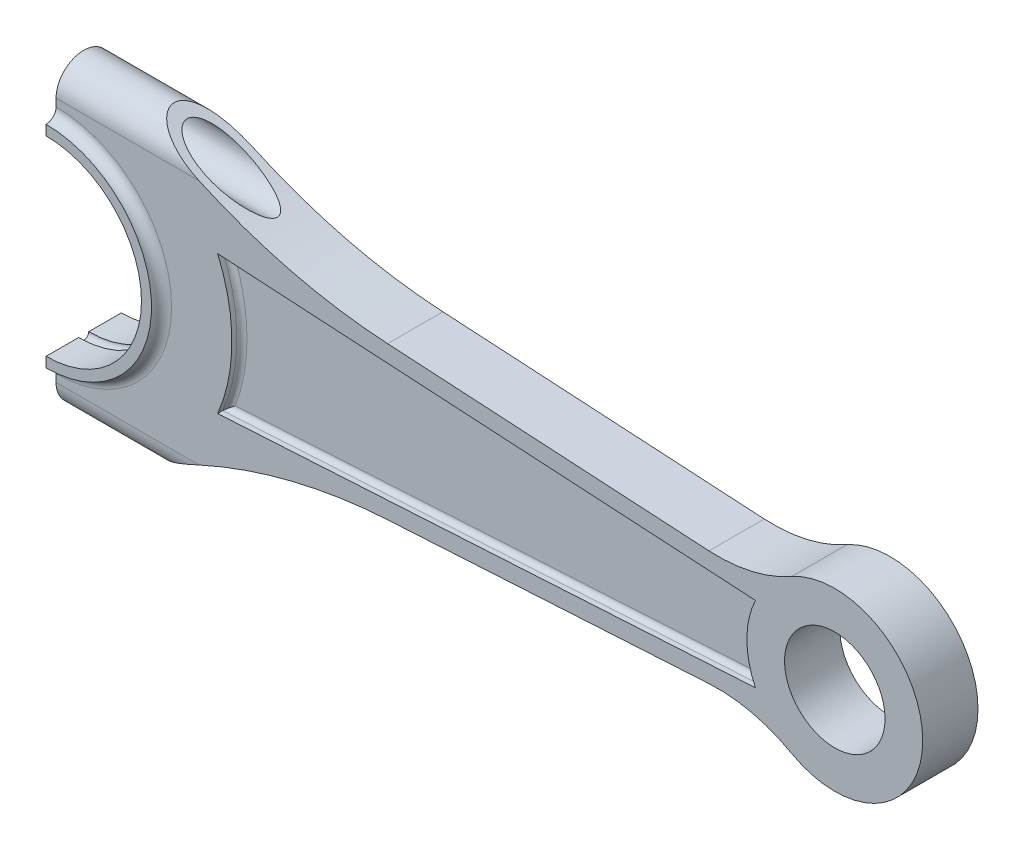
SolidWorks part; units mm, degrees
ref_plane "Front Plane" through (0, 0, 0) normal (0, 0, 1) x (1, 0, 0)
ref_plane "Top Plane" through (0, 0, 0) normal (0, 1, 0) x (1, 0, 0)
ref_plane "Right Plane" through (0, 0, 0) normal (1, 0, 0) x (0, 0, -1)
sketch "Sketch1" plane through (0, 0, 0) normal (0, 0, 1) x (1, 0, 0)
  line L0 (3937, 0) -> (0, 0) construction
  line L1 (-0.057, 762) -> (457.905, 762)
  line L2 (757.2512, 439.1989) -> (773.4704, 438.2517)
  line L3 (1676.1325, 385.5364) -> (3300.7334, 290.6599)
  line L4 (1676.1325, -385.5364) -> (3300.7334, -290.6599)
  line L5 (-0.057, -762) -> (457.905, -762)
  line L6 (-0.057, 762) -> (0, 482.6)
  line L7 (-0.057, -762) -> (0, -482.6)
  arc A0 (0, -482.6) -> (0, 482.6) centre (0, 0) ccw
  circle A1 centre (3937, 0) radius 254
  arc A2 (3718.9531, -387.3446) -> (3718.9531, 387.3446) centre (3937, 0) ccw
  arc A3 (457.905, 762) -> (457.905, -762) centre (0, 0) ccw construction
  arc A4 (3300.7334, 290.6599) -> (3718.9531, 387.3446) centre (3345.1584, 1051.3638) ccw
  arc A5 (457.905, 762) -> (1676.1325, 385.5364) centre (1831.62, 3048) ccw
  arc A6 (3300.7334, -290.6599) -> (3718.9531, -387.3446) centre (3345.1584, -1051.3638) cw
  arc A7 (457.905, -762) -> (1676.1325, -385.5364) centre (1831.62, -3048) cw
  dimension "D1" = 965.2
  dimension "D2" = 508
  dimension "D3" = 889
  dimension "D6" = 1778
  dimension "D9" = 762
  dimension "D10" = 2667
  dimension "D4" = 762
  dimension "D5" = 457.962
  dimension "D7" = 0
  dimension "D8" = 3937
extrude "Boss-Extrude1" add sketch "Sketch1" along normal mid plane 279.4 contours L5 A7 L4 A6 A2 A4 L3 A5 L1 L6 A0 L7 A1 region at (1893.6436, 0, 0)
sketch "Sketch3" plane through (0, 0, 139.7) normal (0, 0, 1) x (1, 0, 0)
  line L0 (3535.7201, -191.1929) -> (817.2234, -349.9527)
  line L1 (1676.1325, -385.5364) -> (3300.7334, -290.6599) construction
  line L2 (3937, 0) -> (0, 0) construction
  line L3 (3535.7201, 191.1929) -> (817.2234, 349.9527)
  arc A1 (3535.7201, 191.1929) -> (3535.7201, -191.1929) centre (3937, 0) ccw
  arc A2 (817.2234, -349.9527) -> (817.2234, 349.9527) centre (0, 0) ccw
  dimension "D1" = 1778
  dimension "D2" = 889
  dimension "D3" = 85.598
extrude "Cut-Extrude1" cut sketch "Sketch3" against normal blind 50.8 and the other way through all
sketch "Sketch4" plane through (0.0984, 0, 0) normal (-1, 0.0002, 0) x (0, 0, 1)
  line L0 (-139.7, 482.6) -> (139.7, 762) construction
  line L1 (-139.7, 762) -> (139.7, 482.6) construction
  line L2 (0, 0) -> (-973.0459, 0) construction
  circle A0 centre (0, 622.3) radius 63.5
  circle A1 centre (0, -622.3) radius 63.5
  dimension "D1" = 127
extrude "Cut-Extrude2" cut sketch "Sketch4" against normal through all both and the other way through all
sketch "Sketch5" plane through (0.0984, 0, 0) normal (-1, -0.0002, 0) x (0, 0, 1)
  circle A0 centre (0, 622.3) radius 101.6
  circle A1 centre (0, -622.3) radius 101.6
  dimension "D1" = 203.2
  dimension "D2" = 203.2
extrude "Cut-Extrude3" cut sketch "Sketch5" against normal through all from offset 508
sketch "Sketch6" plane through (0, 0, 139.7) normal (0, 0, 1) x (1, 0, 0)
  line L0 (-0.057, 762) -> (0, 482.6) construction
  line L1 (-0.057, -762) -> (0, -482.6) construction
  line L2 (-0.0104, 533.4) -> (0, 482.6)
  line L3 (0, -482.6) -> (-0.0104, -533.4)
  arc A0 (0, -482.6) -> (0, 482.6) centre (0, 0) ccw construction
  arc A1 (0, -482.6) -> (0, 482.6) centre (0, 0) ccw
  arc A2 (-0.0104, 533.4) -> (-0.0104, -533.4) centre (0, 0) cw
  dimension "D1" = 533.4
extrude "Boss-Extrude2" add sketch "Sketch6" along normal blind 50.8
mirror "Mirror1" about plane through (0, 0, 0) normal (0, 0, 1) of "Cut-Extrude1", "Boss-Extrude2"
fillet "Fillet1" radius 50.8 2 edges at (533.4, 0, -139.7) (533.4, 0, 139.7)
sketch "Sketch8" plane through (0.0984, 0, 0) normal (-1, -0.0002, 0) x (0, 0, 1)
  line L0 (190.5, 482.6) -> (-190.5, 482.6) construction
  line L1 (0, 0) -> (764.7578, 0) construction
  circle A0 centre (0, 482.6) radius 25.4
  dimension "D1" = 50.8
revolve "Cut-Revolve1" cut sketch "Sketch8" angle 360 about L1
fillet "Fillet3" radius 25.4 8 edges at (3492.5, 0, 88.9) (2176.4718, 270.5728, 88.9) (2176.4718, -270.5728, 88.9) (889, 0, 88.9) (2176.4718, -270.5728, -88.9) (889, 0, -88.9) (3492.5, 0, -88.9) (2176.4718, 270.5728, -88.9)
fillet "Fillet4" 2 edges at (228.924, 762, 139.7) (228.924, 762, -139.7) type full round first side face at (1626.8583, 0, 139.7) second side face at (2176.4718, 0, -139.7) middle face at (228.924, 762, 0)
fillet "Fillet5" 2 edges at (228.924, -762, 139.7) (228.924, -762, -139.7) type full round first side face at (1649.9448, -20.8142, 139.7) second side face at (2176.4718, 0, -139.7) middle face at (228.924, -762, 0)
